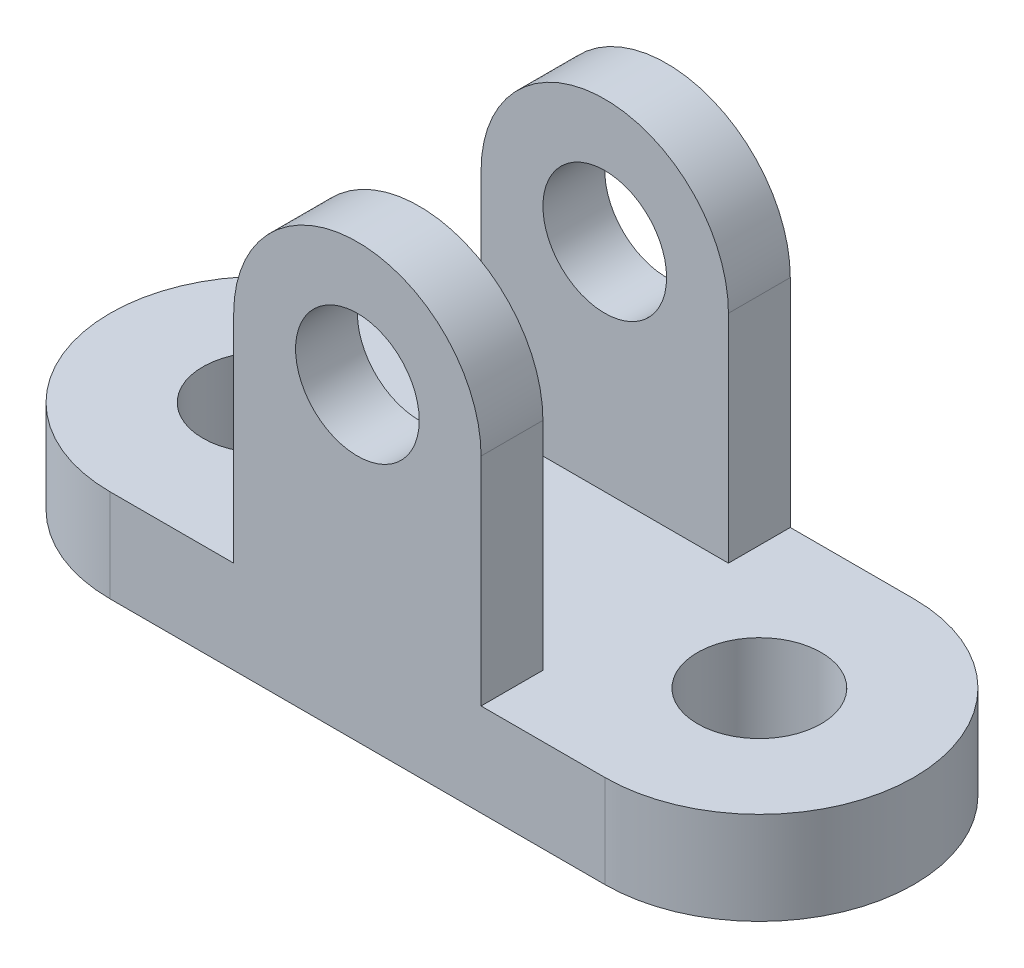
SolidWorks part; units mm, degrees
ref_plane "Front Plane" through (0, 0, 0) normal (0, 0, 1) x (1, 0, 0)
ref_plane "Top Plane" through (0, 0, 0) normal (0, 1, 0) x (1, 0, 0)
ref_plane "Right Plane" through (0, 0, 0) normal (1, 0, 0) x (0, 0, -1)
sketch "Sketch1" plane through (0, 0, 0) normal (0, 1, 0) x (1, 0, 0)
  line L0 (-40, 0) -> (40, 0) construction
  line L1 (-40, 25) -> (40, 25)
  line L2 (-40, -25) -> (40, -25)
  arc A0 (-40, 25) -> (-40, -25) centre (-40, 0) ccw
  arc A1 (40, -25) -> (40, 25) centre (40, 0) ccw
  point P3 (0, 0)
  point P8 (0, 0)
  dimension "D1" = 25
  dimension "D2" = 80
extrude "Boss-Extrude1" add sketch "Sketch1" along normal blind 15
sketch "Sketch3" plane through (0, 0, 0) normal (0, 0, 1) x (1, 0, 0)
  line L0 (-40, 15) -> (40, 15) construction
  line L1 (-20, 70) -> (20, 70)
  line L2 (-20, 70) -> (-20, 15)
  line L3 (-20, 15) -> (20, 15)
  line L4 (20, 70) -> (20, 15)
  dimension "D1" = 40
  dimension "D2" = 20
  dimension "D3" = 55
extrude "Boss-Extrude2" add sketch "Sketch3" along normal mid plane 50
fillet "Fillet1" 2 edges at (20, 70, 0) (-20, 70, 0) type full round first side face at (20, 42.5, 0) second side face at (-20, 42.5, 0) middle face at (0, 70, 0)
sketch "Sketch4" plane through (0, 15, 0) normal (0, 1, 0) x (1, 0, 0)
  line L0 (40, 25) -> (20, 25) construction
  line L1 (-60.1608, 15) -> (77.9663, 15)
  line L2 (-60.1608, 15) -> (-60.1608, -15)
  line L3 (-60.1608, -15) -> (77.9663, -15)
  line L4 (77.9663, 15) -> (77.9663, -15)
  line L5 (20, -25) -> (40, -25) construction
  dimension "D1" = 10
  dimension "D2" = 10
extrude "Cut-Extrude1" cut sketch "Sketch4" along normal through all
hole_wizard "Ø1.0mm Dowel Hole1" positions "Sketch5" profile "Sketch6" hole size "Ø1.0" standard "ISO" end condition through all
sketch "Sketch5" plane through (0, 15, 0) normal (0, 1, 0) x (1, 0, 0)
  point P0 (40, 0)
  point P3 (-40, 0)
sketch "Sketch6" plane through (40, 15, 0) normal (1, 0, 0) x (0, 0, 1)
  line L0 (0, 0) -> (0, 15)
  line L1 (0, 15) -> (10, 15)
  line L2 (10, 15) -> (10, 0)
  line L5 (10, 0) -> (0, 0)
  line L11 (0, -6.35) -> (0, 107.95) construction
  dimension "Thru Hole Dia." = 20
  dimension "Thru Hole Depth" = 15
hole_wizard "Ø1.0mm Dowel Hole2" positions "Sketch7" profile "Sketch8" hole size "Ø1.0" standard "ISO" end condition through all
sketch "Sketch7" plane through (0, 0, 25) normal (0, 0, 1) x (1, 0, 0)
  point P0 (0, 50)
sketch "Sketch8" plane through (0, 50, 25) normal (1, 0, 0) x (0, -1, 0)
  line L0 (0, 0) -> (0, 50)
  line L1 (0, 50) -> (10, 50)
  line L2 (10, 50) -> (10, 0)
  line L5 (10, 0) -> (0, 0)
  line L11 (0, -6.35) -> (0, 107.95) construction
  dimension "Thru Hole Dia." = 20
  dimension "Thru Hole Depth" = 50
